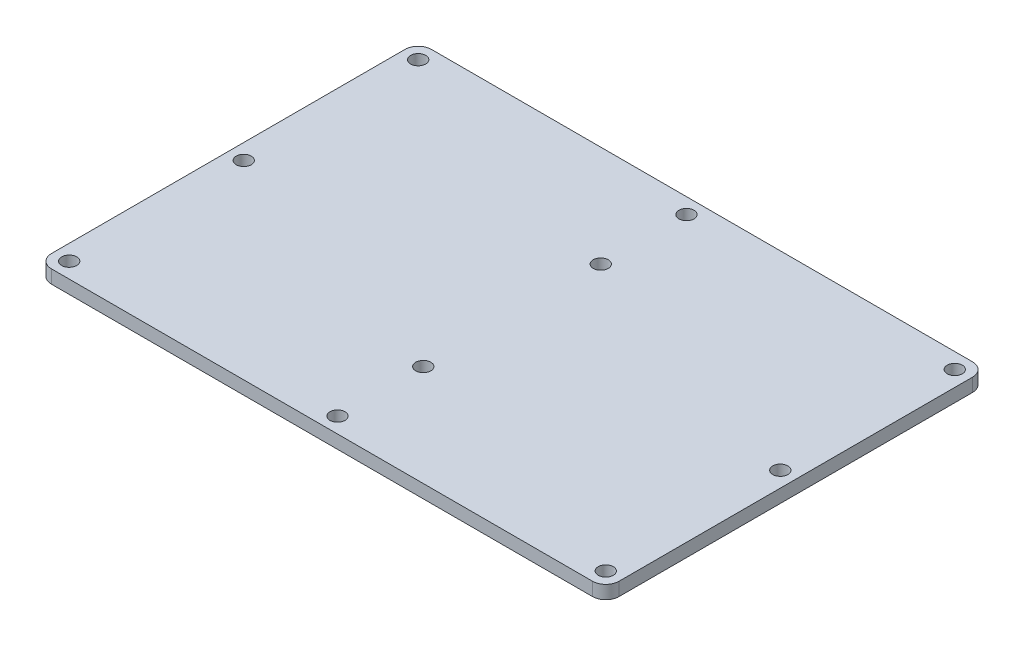
SolidWorks part; units mm, degrees
ref_plane "Front Plane" through (0, 0, 0) normal (0, 0, 1) x (1, 0, 0)
ref_plane "Top Plane" through (0, 0, 0) normal (0, 1, 0) x (1, 0, 0)
ref_plane "Right Plane" through (0, 0, 0) normal (1, 0, 0) x (0, 0, -1)
sketch "Sketch1" plane through (0, 0, 0) normal (0, 1, 0) x (1, 0, 0)
  line L1 (-64, -42.85) -> (64, -42.85)
  line L2 (-64, -42.85) -> (-64, 42.85)
  line L3 (-64, 42.85) -> (64, 42.85)
  line L4 (64, -42.85) -> (64, 42.85)
  line L5 (-64, -42.85) -> (64, 42.85) construction
  line L6 (-64, 42.85) -> (64, -42.85) construction
  point P0 (0, 0)
  dimension "D1" = 85.7
  dimension "D2" = 128
extrude "Boss-Extrude1" add sketch "Sketch1" along normal blind 3
hole_wizard "M3 Clearance Hole1" positions "Sketch2" profile "Sketch3" hole size "M3" standard "ANSI Metric" end condition through all
sketch "Sketch2" plane through (0, 3, 0) normal (0, 1, 0) x (1, 0, 0)
  line L0 (0, -1.65) -> (0, 1.65) construction
  line L1 (-1.65, 0) -> (1.65, 0) construction
  line L2 (64, 42.85) -> (-64, 42.85) construction
  line L3 (-64, 42.85) -> (-64, -42.85) construction
  line L4 (64, -42.85) -> (64, 42.85) construction
  line L5 (-64, -42.85) -> (64, -42.85) construction
  point P0 (-60.5, 39.35)
  point P2 (0, 39.35)
  point P6 (60.5, 39.35)
  point P8 (60.5, 0)
  point P12 (60.5, -39.35)
  point P14 (0, -39.35)
  point P16 (-60.5, -39.35)
  point P18 (-60.5, 0)
  point P20 (0, -20.01)
  point P22 (0, 20.01)
  dimension "D1" = 3.5
  dimension "D2" = 3.5
  dimension "D3" = 3.5
  dimension "D4" = 3.5
  dimension "D5" = 19.34
  dimension "D6" = 19.34
sketch "Sketch3" plane through (-60.5, 3, -39.35) normal (1, 0, 0) x (0, 0, 1)
  line L0 (0, 0) -> (0, 3)
  line L1 (0, 3) -> (1.7, 3)
  line L2 (1.7, 3) -> (1.7, 0)
  line L5 (1.7, 0) -> (0, 0)
  line L11 (0, -6.35) -> (0, 107.95) construction
  dimension "Thru Hole Dia." = 3.4
  dimension "Thru Hole Depth" = 3
fillet "Fillet1" radius 3 4 edges at (64, 1.5, -42.85) (64, 1.5, 42.85) (-64, 1.5, -42.85) (-64, 1.5, 42.85)
equation "\"D2@Sketch2\"=\"D1@Sketch2\""
equation "\"D3@Sketch2\"=\"D1@Sketch2\""
equation "\"D4@Sketch2\"=\"D1@Sketch2\""
equation "\"D6@Sketch2\"=\"D5@Sketch2\""
